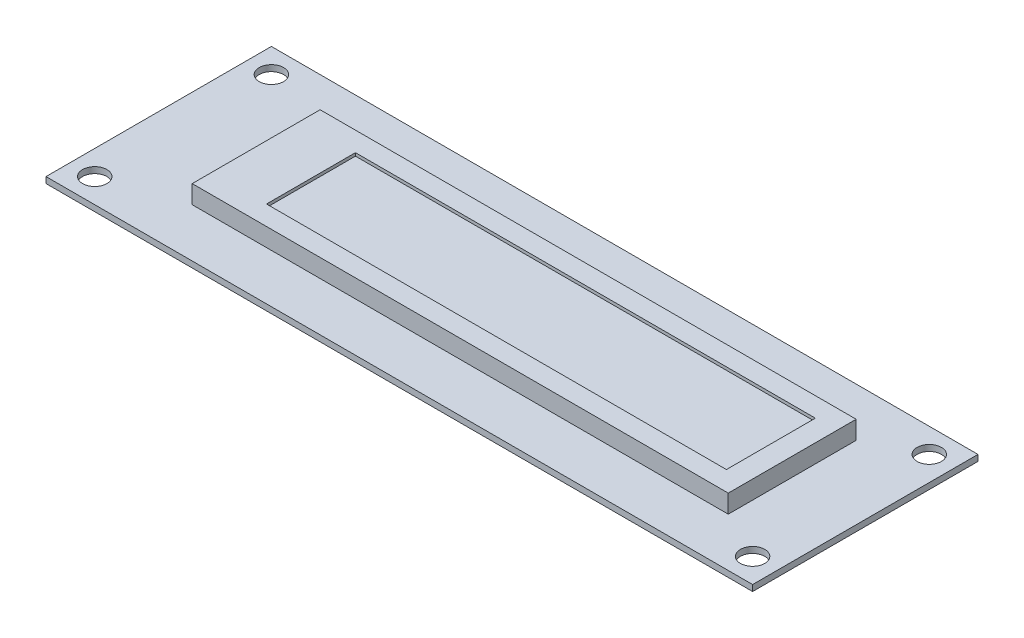
SolidWorks part; units mm, degrees
ref_plane "Front" through (0, 0, 0) normal (0, 0, 1) x (1, 0, 0)
ref_plane "Top" through (0, 0, 0) normal (0, 1, 0) x (1, 0, 0)
ref_plane "Right" through (0, 0, 0) normal (1, 0, 0) x (0, 0, -1)
sketch "Sketch1" plane through (0, 0, 0) normal (0, 1, 0) x (1, 0, 0)
  line L1 (-58, 18.5) -> (58, 18.5)
  line L2 (-58, 18.5) -> (-58, -18.5)
  line L3 (-58, -18.5) -> (58, -18.5)
  line L4 (58, 18.5) -> (58, -18.5)
  line L5 (-58, 18.5) -> (58, -18.5) construction
  line L6 (-58, -18.5) -> (58, 18.5) construction
  point P0 (0, 0)
  dimension "D1" = 37
  dimension "D2" = 116
extrude "Boss-Extrude1" add sketch "Sketch1" along normal blind 1
sketch "Sketch2" plane through (0, 1, 0) normal (0, 1, 0) x (1, 0, 0)
  line L0 (-58, 18.5) -> (-58, -18.5) construction
  line L1 (-42, 10.5) -> (46, 10.5)
  line L2 (-42, 10.5) -> (-42, -10.5)
  line L3 (-42, -10.5) -> (46, -10.5)
  line L4 (46, 10.5) -> (46, -10.5)
  line L5 (-42, 10.5) -> (46, -10.5) construction
  line L6 (-42, -10.5) -> (46, 10.5) construction
  point P0 (2, 0)
  dimension "D1" = 21
  dimension "D2" = 0
  dimension "D3" = 88
  dimension "D4" = 16
extrude "Boss-Extrude2" add sketch "Sketch2" along normal blind 3
sketch "Sketch3" plane through (0, 4, 0) normal (0, 1, 0) x (1, 0, 0)
  line L1 (-33, 7.3) -> (42.5, 7.3)
  line L2 (-33, 7.3) -> (-33, -7.3)
  line L3 (-33, -7.3) -> (42.5, -7.3)
  line L4 (42.5, 7.3) -> (42.5, -7.3)
  line L5 (46, 10.5) -> (-42, 10.5) construction
  line L6 (-42, -10.5) -> (46, -10.5) construction
  line L8 (46, -10.5) -> (46, 10.5) construction
  line L9 (-42, 10.5) -> (-42, -10.5) construction
  point P4 (42.5, 0)
  dimension "D1" = 3.5
  dimension "D2" = 3.2
  dimension "D3" = 3.2
  dimension "D4" = 9
extrude "Cut-Extrude1" cut sketch "Sketch3" against normal blind 0.5
sketch "Sketch4" plane through (0, 1, 0) normal (0, 1, 0) x (1, 0, 0)
  line L0 (58, -18.5) -> (58, 18.5) construction
  line L1 (-58, -18.5) -> (58, -18.5) construction
  circle A0 centre (54, -14.5) radius 2
  dimension "D1" = 4
  dimension "D2" = 4
  dimension "D3" = 4
extrude "Cut-Extrude2" cut sketch "Sketch4" against normal blind 10
mirror "Mirror1" about plane through (0, 0, 0) normal (1, 0, 0) of "Cut-Extrude2"
mirror "Mirror2" about plane through (0, 0, 0) normal (0, 0, 1) of "Mirror1"
